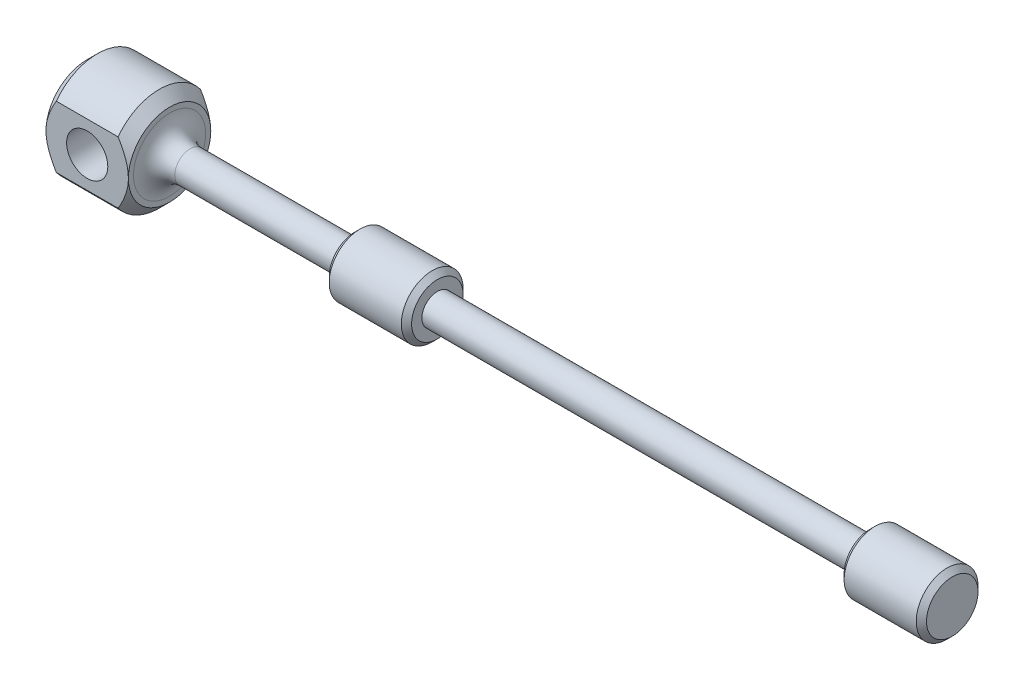
SolidWorks part; units mm, degrees
ref_plane "Front Plane" through (0, 0, 0) normal (0, 0, 1) x (1, 0, 0)
ref_plane "Top Plane" through (0, 0, 0) normal (0, 1, 0) x (1, 0, 0)
ref_plane "Right Plane" through (0, 0, 0) normal (1, 0, 0) x (0, 0, -1)
sketch "Sketch1" plane through (0, 0, 0) normal (1, 0, 0) x (0, 0, -1)
  circle A0 centre (0, 0) radius 1.5
  dimension "D1" = 3
extrude "Boss-Extrude1" add sketch "Sketch1" along normal mid plane 76
sketch "Sketch2" plane through (38, 0, 0) normal (1, 0, 0) x (0, 0, -1)
  circle A0 centre (0, 0) radius 3
  dimension "D1" = 6
extrude "Boss-Extrude2" add sketch "Sketch2" along normal blind 8
extrude "Boss-Extrude3" add sketch "Sketch2<2>" along normal blind 8 from offset 50 offset against normal yes
sketch "Sketch2<2>" plane through (38, 0, 0) normal (1, 0, 0) x (0, 0, -1) same geometry as "Sketch2"
chamfer "Chamfer1" distance 0.5 angle 45 4 edges at (38, 0, -3) (46, 0, -3) (-12, 0, -3) (-4, 0, -3)
sketch "Sketch3" plane through (-38, 0, 0) normal (-1, 0, 0) x (0, 0, 1)
  circle A0 centre (0, 0) radius 5
  dimension "D1" = 10
extrude "Boss-Extrude4" add sketch "Sketch3" against normal blind 8
sketch "Sketch4" plane through (-38, 0, 0) normal (-1, 0, 0) x (0, 0, 1)
  line L0 (-4, 3) -> (-4, -3)
  line L1 (4, 3) -> (4, -3)
  arc A0 (4, -3) -> (4, 3) centre (0, 0) ccw
  arc A1 (-4, 3) -> (-4, -3) centre (0, 0) ccw
  dimension "D1" = 10
  dimension "D2" = 4
  dimension "D3" = 4
extrude "Cut-Extrude1" cut sketch "Sketch4" against normal blind 8
sketch "Sketch5" plane through (0, 0, 4) normal (0, 0, 1) x (1, 0, 0)
  line L0 (-38, 0) -> (-30, 0) construction
  line L1 (-38, 3) -> (-38, -3) construction
  line L2 (-30, 3) -> (-30, -3) construction
  circle A0 centre (-34, 0) radius 2
  dimension "D1" = 4
extrude "Cut-Extrude2" cut sketch "Sketch5" against normal through all
chamfer "Chamfer3" distance 1 angle 45 2 edges at (-38, -5, 0) (-38, 5, 0)
fillet "Fillet1" radius 2 1 edges at (-30, 0, 1.5)
chamfer "Chamfer4" distance 1 angle 45 2 edges at (-30, -5, 0) (-30, 5, 0)
